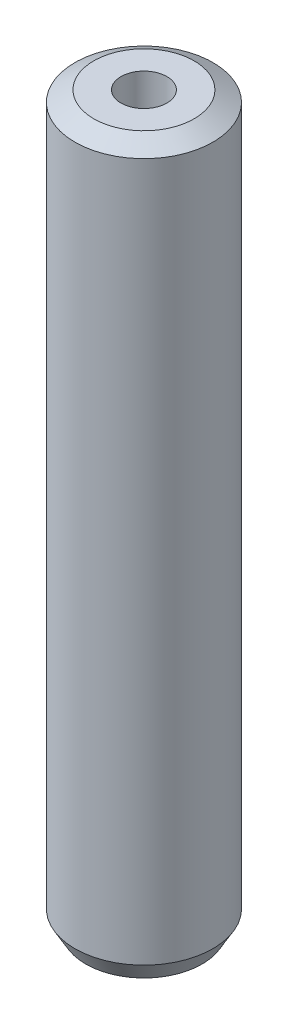
SolidWorks part; units mm, degrees
ref_plane "Front Plane" through (0, 0, 0) normal (0, 0, 1) x (1, 0, 0)
ref_plane "Top Plane" through (0, 0, 0) normal (0, 1, 0) x (1, 0, 0)
ref_plane "Right Plane" through (0, 0, 0) normal (1, 0, 0) x (0, 0, -1)
sketch "Sketch1" plane through (0, 0, 0) normal (0, 1, 0) x (1, 0, 0)
  circle A0 centre (0, 0) radius 35
  dimension "SHAFT_OD" = 70
extrude "Boss-Extrude1" add sketch "Sketch1" along normal blind 369.298
sketch "Sketch2" plane through (0, 0, 0) normal (0, 1, 0) x (1, 0, 0)
  circle A0 centre (0, 0) radius 11.6513
  dimension "BORE_D" = 23.3026
extrude "Cut-Extrude1" cut sketch "Sketch2" along normal through all
chamfer "Chamfer1" distance 5.5036 angle 60 2 edges at (0, 369.298, 35) (0, 0, 35) first distance on face at (0, 369.298, 35) first distance on face at (0, 0, 11.6513)
